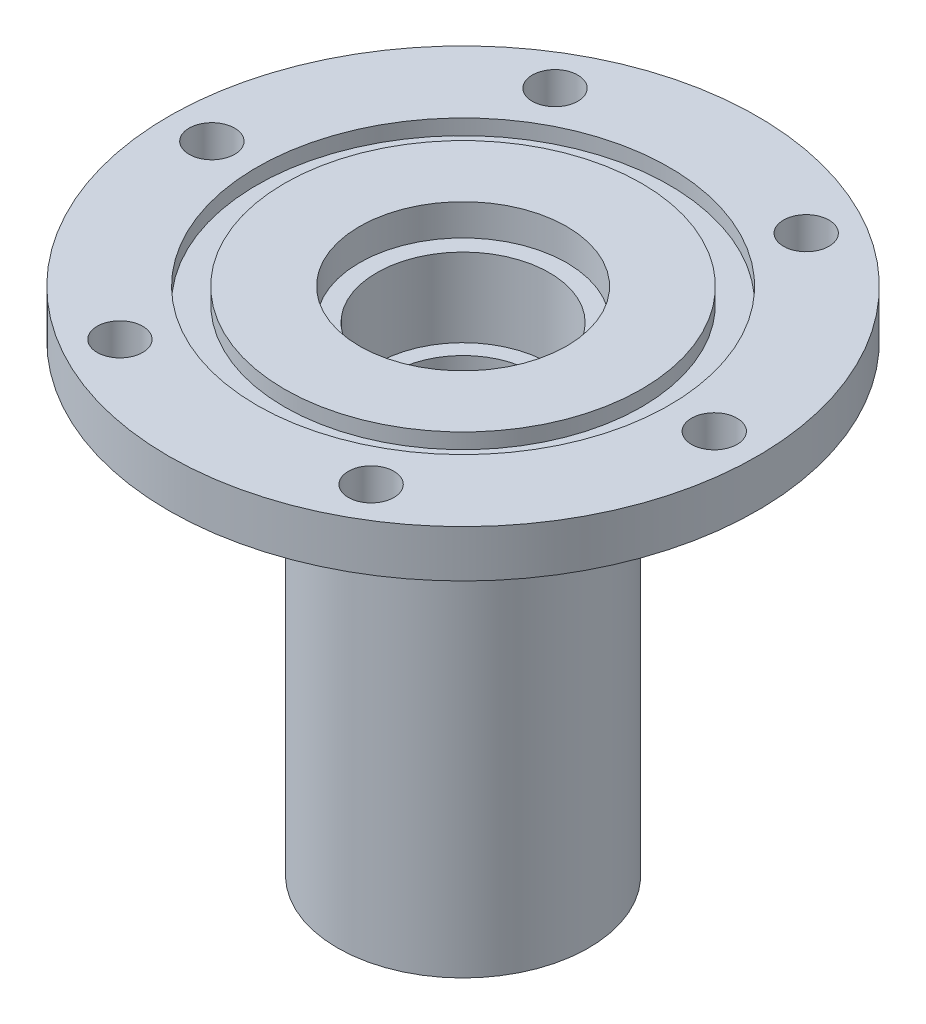
SolidWorks part; units mm, degrees
ref_plane "Front Plane" through (0, 0, 0) normal (0, 0, 1) x (1, 0, 0)
ref_plane "Top Plane" through (0, 0, 0) normal (0, 1, 0) x (1, 0, 0)
ref_plane "Right Plane" through (0, 0, 0) normal (1, 0, 0) x (0, 0, -1)
sketch "Sketch1" plane through (0, 0, 0) normal (0, 0, 1) x (1, 0, 0)
  line L0 (0, 0) -> (0, -122.9972) construction
  line L1 (37.5, 0) -> (26.2636, 0)
  line L2 (13.2, 0) -> (13.2, -4)
  line L3 (13.2, -4) -> (11, -4)
  line L4 (11, -4) -> (11, -14)
  line L9 (12.5, -65) -> (16, -65)
  line L10 (16, -65) -> (16, -6)
  line L11 (16, -6) -> (37.5, -6)
  line L12 (37.5, -6) -> (37.5, 0)
  line L23 (22.733, 0) -> (22.733, -1.9558)
  line L24 (22.733, -1.9558) -> (26.2636, -1.9558)
  line L25 (26.2636, -1.9558) -> (26.2636, 0)
  line L26 (22.733, 0) -> (13.2, 0)
  line L27 (11, -14) -> (9, -14)
  line L28 (9, -14) -> (9, -17)
  line L29 (9, -17) -> (11, -17)
  line L30 (11, -17) -> (11, -30.5)
  line L31 (12.5, -65) -> (12.5, -30.5)
  line L32 (12.5, -30.5) -> (11, -30.5)
  point P17 (0, 0)
  dimension "D1" = 22
  dimension "D2" = 26.4
  dimension "D3" = 4
  dimension "D4" = 18
  dimension "D5" = 14
  dimension "D6" = 3
  dimension "D7" = 25
  dimension "D8" = 65
  dimension "D9" = 6
  dimension "D10" = 32
  dimension "D11" = 75
  dimension "D12" = 52.5272
  dimension "D13" = 1.9558
  dimension "D14" = 3.5306
  dimension "D15" = 13.5
revolve "Revolve1" add sketch "Sketch1" angle 360 about L0
sketch "Sketch2" plane through (0, 0, 0) normal (0, 1, 0) x (1, 0, 0)
  line L1 (32, 0) -> (16, 27.7128)
  line L2 (16, 27.7128) -> (-16, 27.7128)
  line L3 (-16, 27.7128) -> (-32, 0)
  line L4 (-32, 0) -> (-16, -27.7128)
  line L5 (-16, -27.7128) -> (16, -27.7128)
  line L6 (16, -27.7128) -> (32, 0)
  circle A0 centre (0, 0) radius 32 construction
  circle A1 centre (32, 0) radius 2.75
  circle A2 centre (32, 0) radius 5
  dimension "D1" = 64
  dimension "D2" = 10
  dimension "D3" = 5.5
hole_wizard "M5 Clearance Hole1" positions "Sketch3" profile "Sketch4" hole size "M5" standard "ANSI Metric" end condition through all
sketch "Sketch3" plane through (0, 0, 0) normal (0, 1, 0) x (1, 0, 0)
  point P0 (16, 27.7128)
  point P3 (32, 0)
  point P6 (16, -27.7128)
  point P9 (-16, -27.7128)
  point P12 (-32, 0)
  point P15 (-16, 27.7128)
sketch "Sketch4" plane through (16, 0, -27.7128) normal (1, 0, 0) x (0, 0, 1)
  line L0 (0, 0) -> (0, 65)
  line L1 (0, 65) -> (2.9, 65)
  line L2 (2.9, 65) -> (2.9, 0)
  line L5 (2.9, 0) -> (0, 0)
  line L11 (0, -6.35) -> (0, 107.95) construction
  dimension "Thru Hole Dia." = 5.8
  dimension "Thru Hole Depth" = 65
